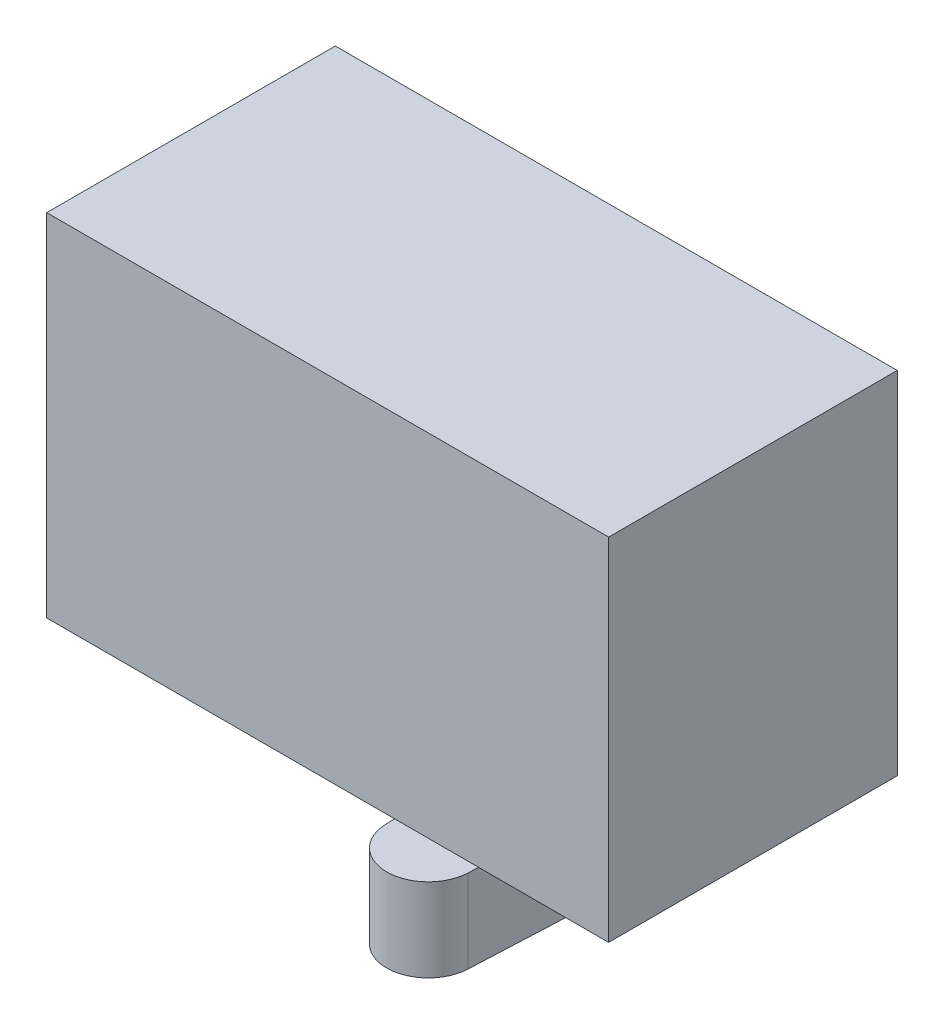
SolidWorks part; units mm, degrees
ref_plane "XY" through (0, 0, 0) normal (0, 0, 1) x (1, 0, 0)
ref_plane "XZ" through (0, 0, 0) normal (0, 1, 0) x (1, 0, 0)
ref_plane "YZ" through (0, 0, 0) normal (1, 0, 0) x (0, 0, -1)
ref_axis "X" through (-15.95, 0, 0) along (1, 0, 0)
ref_axis "Y" through (0, -22.47, 0) along (0, 1, 0)
ref_axis "Z" through (0, 0, 15.4) along (0, 0, -1)
sketch "Sketch1" plane through (0, 0, 0) normal (0, 0, 1) x (1, 0, 0)
  line L1 (-20.25, -12.65) -> (20.25, -12.65)
  line L2 (-20.25, -12.65) -> (-20.25, 12.65)
  line L3 (-20.25, 12.65) -> (20.25, 12.65)
  line L4 (20.25, -12.65) -> (20.25, 12.65)
  line L5 (-20.25, -12.65) -> (20.25, 12.65) construction
  line L6 (-20.25, 12.65) -> (20.25, -12.65) construction
  point P0 (0, 0)
  dimension "D1" = 25.3
  dimension "D2" = 40.5
extrude "Boss-Extrude1" add sketch "Sketch1" along normal mid plane 20.8
sketch "Sketch3" plane through (0, -12.65, 0) normal (0, -1, 0) x (1, 0, 0)
  line L0 (4.3536, -0.1591) -> (4.8531, -11.1364)
  line L1 (10.8469, -11.1364) -> (11.3464, -0.1591)
  line L2 (11.3464, 0.1591) -> (10.8469, 11.1364)
  line L3 (4.8531, 11.1364) -> (4.3536, 0.1591)
  line L4 (7.85, -11) -> (7.85, 11) construction
  line L5 (11.35, 0) -> (4.35, 0) construction
  line L6 (0, 0) -> (7.85, 0) construction
  line L7 (17.65, 0) -> (-17.65, 0) construction
  arc A1 (4.8531, -11.1364) -> (10.8469, -11.1364) centre (7.85, -11) ccw
  arc A2 (10.8469, 11.1364) -> (4.8531, 11.1364) centre (7.85, 11) ccw
  arc A3 (4.3536, 0.1591) -> (4.3536, -0.1591) centre (7.85, 0) ccw
  arc A4 (11.3464, -0.1591) -> (11.3464, 0.1591) centre (7.85, 0) ccw
  circle A5 centre (7.85, 0) radius 11 construction
  point P19 (0, 0)
  dimension "D2" = 11
  dimension "D3" = 3.5
  dimension "D1" = 3
  dimension "D4" = 35.3
  dimension "D5" = 9.8
extrude "Boss-Extrude2" add sketch "Sketch3" along normal blind 6 separate body contours L3 A3 L0 A1 L1 A4 L2 A2
